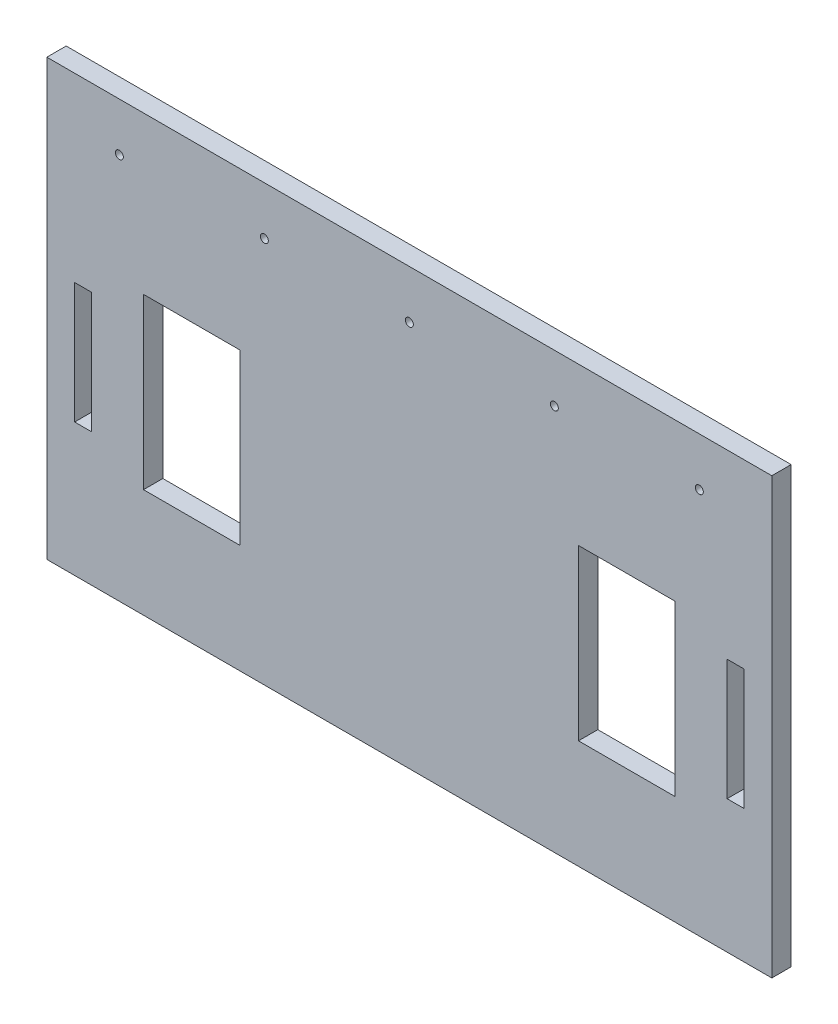
SolidWorks part; units mm, degrees
ref_plane "Front" through (0, 0, 0) normal (0, 0, 1) x (1, 0, 0)
ref_plane "Top" through (0, 0, 0) normal (0, 1, 0) x (1, 0, 0)
ref_plane "Right" through (0, 0, 0) normal (1, 0, 0) x (0, 0, -1)
sketch "Esquisse1" plane through (0, 0, 0) normal (0, 0, 1) x (1, 0, 0)
  line L1 (0, 0) -> (300, 0)
  line L2 (0, 0) -> (0, 180)
  line L3 (0, 180) -> (300, 180)
  line L4 (300, 0) -> (300, 180)
  dimension "D1" = 300
  dimension "D2" = 180
extrude "Boss.-Extru.1" add sketch "Esquisse1" along normal blind 8
sketch "Esquisse2" plane through (0, 0, 8) normal (0, 0, 1) x (1, 0, 0)
  line L0 (150, 180) -> (150, 0) construction
  line L1 (40, 45) -> (80, 45)
  line L2 (40, 45) -> (40, 115)
  line L3 (40, 115) -> (80, 115)
  line L4 (80, 45) -> (80, 115)
  line L5 (300, 180) -> (0, 180) construction
  line L6 (0, 0) -> (300, 0) construction
  line L7 (80, 80) -> (150, 80) construction
  line L8 (60, 45) -> (60, 115) construction
  line L9 (40, 80) -> (18.5, 80) construction
  line L10 (15, 55) -> (15, 105) construction
  line L11 (11.5, 55) -> (18.5, 55)
  line L12 (11.5, 55) -> (11.5, 105)
  line L13 (11.5, 105) -> (18.5, 105)
  line L14 (18.5, 55) -> (18.5, 105)
  line L15 (285, 55) -> (285, 105) construction
  line L16 (260, 80) -> (281.5, 80) construction
  line L17 (240, 45) -> (240, 115) construction
  line L18 (281.5, 55) -> (281.5, 105)
  line L19 (288.5, 105) -> (281.5, 105)
  line L20 (288.5, 55) -> (288.5, 105)
  line L21 (288.5, 55) -> (281.5, 55)
  line L22 (220, 45) -> (220, 115)
  line L23 (260, 115) -> (220, 115)
  line L24 (260, 45) -> (260, 115)
  line L25 (260, 45) -> (220, 45)
  dimension "D1" = 100
  dimension "D2" = 70
  dimension "D3" = 40
  dimension "D4" = 180
  dimension "D5" = 7
  dimension "D6" = 50
  dimension "D7" = 270
extrude "Enlèv. mat.-Extru.1" cut sketch "Esquisse2" against normal through all
sketch "Esquisse3" plane through (0, 0, 8) normal (0, 0, 1) x (1, 0, 0)
  line L0 (0, 160) -> (300, 160) construction
  line L1 (0, 180) -> (0, 0) construction
  line L2 (300, 0) -> (300, 180) construction
  line L3 (180, 160) -> (180, 172.6988) construction
  line L4 (300, 180) -> (0, 180) construction
  line L5 (150, 160) -> (150, 176.3559) construction
  circle A0 centre (270, 160) radius 1.65
  circle A1 centre (210, 160) radius 1.65
  circle A2 centre (150, 160) radius 1.65
  circle A3 centre (90, 160) radius 1.65
  circle A4 centre (30, 160) radius 1.65
  dimension "D1" = 3.3
  dimension "D2" = 60
  dimension "D3" = 60
  dimension "D5" = 60
  dimension "D4" = 20
extrude "Enlèv. mat.-Extru.2" cut sketch "Esquisse3" against normal up to vertex (8 mm away) up to point (300, 180, 0)
